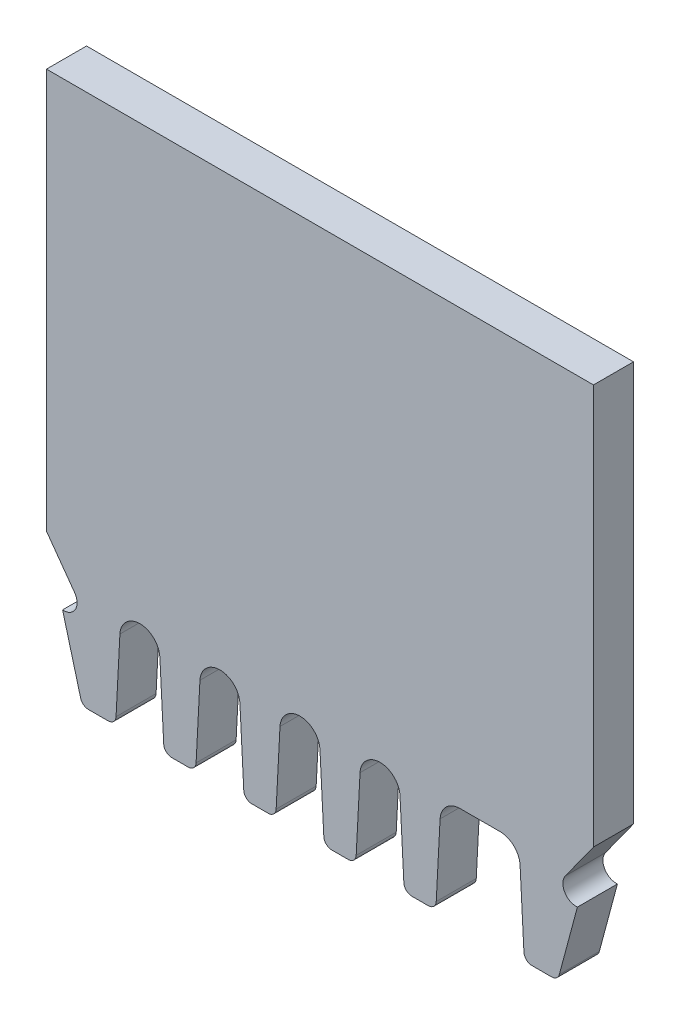
SolidWorks part; units mm, degrees
ref_plane "Front Plane" through (0, 0, 0) normal (0, 0, 1) x (1, 0, 0)
ref_plane "Top Plane" through (0, 0, 0) normal (0, 1, 0) x (1, 0, 0)
ref_plane "Right Plane" through (0, 0, 0) normal (1, 0, 0) x (0, 0, -1)
sketch "Sketch1" plane through (0, 0, 0) normal (0, 0, 1) x (1, 0, 0)
  line L0 (0, 0) -> (0, 20) construction
  line L1 (0, 20) -> (20.5, 20) construction
  line L2 (20.5, 20) -> (20.5, 0) construction
  line L3 (20.5, 0) -> (0, 0) construction
  line L4 (0, 3) -> (20.5, 3) construction
  line L5 (0, 5) -> (20.5, 5) construction
  line L6 (2, 5) -> (2, 0) construction
  line L7 (5, 5) -> (5, 0) construction
  line L8 (8, 5) -> (8, 0) construction
  line L9 (11, 5) -> (11, 0) construction
  line L10 (14, 5) -> (14, 0) construction
  line L11 (18.5, 5) -> (18.5, 0) construction
  line L12 (2, 2.5) -> (5, 2.5) construction
  line L13 (5, 2.5) -> (8, 2.5) construction
  line L14 (8, 2.5) -> (11, 2.5) construction
  line L15 (11, 2.5) -> (14, 2.5) construction
  line L16 (14, 2.5) -> (18.5, 2.5) construction
  line L17 (2, 2.5) -> (0, 2.5) construction
  line L18 (18.5, 2.5) -> (20.5, 2.5) construction
  line L19 (3.5, 2.5) -> (3.5, 0) construction
  line L20 (6.5, 2.5) -> (6.5, 0) construction
  line L21 (9.5, 2.5) -> (9.5, 0) construction
  line L22 (12.5, 2.5) -> (12.5, 0) construction
  line L23 (16.25, 2.5) -> (16.25, 0) construction
  line L24 (15.5, 3.75) -> (17, 3.75)
  line L25 (0, 5) -> (1.3397, 0) construction
  line L26 (1.3397, 0) -> (2.5917, 0)
  line L27 (2.5917, 0) -> (2.751, 3.0393)
  line L28 (4.249, 3.0393) -> (4.4083, 0)
  line L29 (4.4083, 0) -> (5.5917, 0)
  line L30 (5.5917, 0) -> (5.751, 3.0393)
  line L31 (7.249, 3.0393) -> (7.4083, 0)
  line L32 (7.4083, 0) -> (8.5917, 0)
  line L33 (8.5917, 0) -> (8.751, 3.0393)
  line L34 (10.249, 3.0393) -> (10.4083, 0)
  line L35 (10.4083, 0) -> (11.5917, 0)
  line L36 (11.5917, 0) -> (11.751, 3.0393)
  line L37 (13.249, 3.0393) -> (13.4083, 0)
  line L38 (13.4083, 0) -> (14.5917, 0)
  line L39 (14.5917, 0) -> (14.751, 3.0393)
  line L40 (17.749, 3.0393) -> (17.9083, 0)
  line L41 (17.9083, 0) -> (19.1603, 0)
  line L42 (19.1603, 0) -> (20.5, 5) construction
  line L43 (1.3397, 0) -> (1.3397, 5) construction
  line L44 (-2.2942, 5) -> (0.8529, 3.183) construction
  line L45 (0, 5) -> (0, 20)
  line L46 (0, 20) -> (20.5, 20)
  line L47 (20.5, 20) -> (20.5, 5)
  line L48 (10.25, 20) -> (10.25, 5) construction
  line L49 (0, 5) -> (-2.2942, 5) construction
  line L50 (0.8529, 3.183) -> (0.6029, 2.75) construction
  line L51 (0.6029, 2.75) -> (-3.0311, 3.7237) construction
  line L52 (-3.0311, 3.7237) -> (-2.2942, 5) construction
  line L53 (1.3397, 0) -> (0.6029, 2.75)
  line L54 (1.0521, 3.5405) -> (1.6905, 2.6549) construction
  line L55 (1.0521, 3.5405) -> (0, 5)
  line L56 (1.6905, 2.6549) -> (0.6029, 2.75) construction
  line L57 (19.4479, 3.5405) -> (20.5, 5)
  line L58 (19.1603, 0) -> (19.8971, 2.75)
  arc A0 (4.249, 3.0393) -> (2.751, 3.0393) centre (3.5, 3) ccw
  arc A1 (7.249, 3.0393) -> (5.751, 3.0393) centre (6.5, 3) ccw
  arc A2 (10.249, 3.0393) -> (8.751, 3.0393) centre (9.5, 3) ccw
  arc A3 (13.249, 3.0393) -> (11.751, 3.0393) centre (12.5, 3) ccw
  arc A4 (14.751, 3.0393) -> (15.5, 3.75) centre (15.5, 3) cw
  arc A5 (17.749, 3.0393) -> (17, 3.75) centre (17, 3) ccw
  circle A6 centre (-2.2942, 5) radius 3.634 construction
  arc A7 (1.0521, 3.5405) -> (0.6029, 2.75) centre (0.6465, 3.2481) cw
  arc A8 (19.4479, 3.5405) -> (19.8971, 2.75) centre (19.8535, 3.2481) ccw
  dimension "D7" = 0.75
  dimension "D16" = 0.5
  dimension "D1" = 3
  dimension "D2" = 5
  dimension "D3" = 15
  dimension "D4" = 3
  dimension "D5" = 2
  dimension "D6" = 4.5
  dimension "D8" = 3
  dimension "D9" = 20.5
  dimension "D10" = 20
  dimension "D11" = 15
  dimension "D12" = 15
  dimension "D13" = 30
  dimension "D14" = 0.5
  dimension "D17" = 70
extrude "Boss-Extrude1" add sketch "Sketch1" along normal blind 1.5
fillet "Fillet1" radius 0.3 12 edges at (19.1603, 0, 0.75) (17.9083, 0, 0.75) (14.5917, 0, 0.75) (13.4083, 0, 0.75) (11.5917, 0, 0.75) (10.4083, 0, 0.75) (8.5917, 0, 0.75) (7.4083, 0, 0.75) (5.5917, 0, 0.75) (4.4083, 0, 0.75) (2.5917, 0, 0.75) (1.3397, 0, 0.75)
